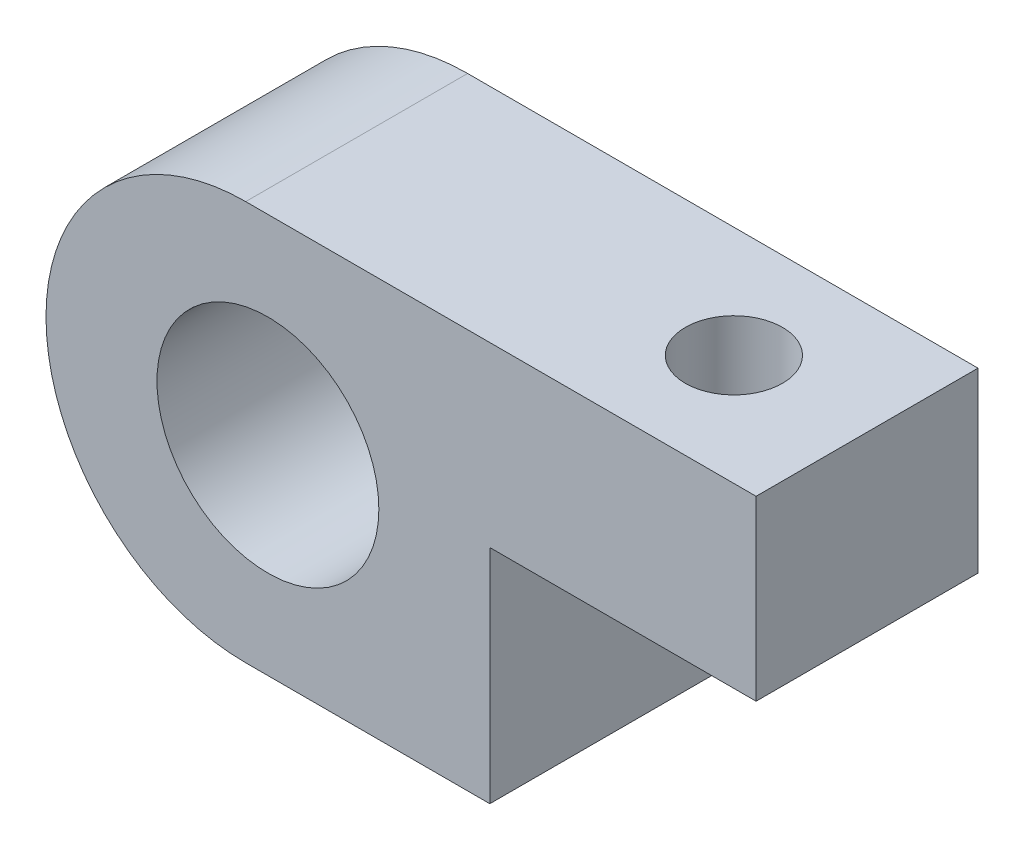
SolidWorks part; units mm, degrees
material "Magnesium Alloy"
ref_plane "Front Plane" through (0, 0, 0) normal (0, 0, 1) x (1, 0, 0)
ref_plane "Top Plane" through (0, 0, 0) normal (0, 1, 0) x (1, 0, 0)
ref_plane "Right Plane" through (0, 0, 0) normal (1, 0, 0) x (0, 0, -1)
sketch "Sketch2" plane through (0, 0, 0) normal (0, 0, 1) x (1, 0, 0)
  line L0 (0, 0) -> (40.64, 0)
  line L1 (40.64, 0) -> (40.64, -10.16)
  line L2 (40.64, -10.16) -> (25.4, -10.16)
  line L3 (25.4, -10.16) -> (25.4, -22.86)
  line L4 (25.4, -22.86) -> (0, -22.86)
  line L5 (0, -22.86) -> (0, 0)
  circle A0 centre (12.7, -11.43) radius 6.35
  dimension "D5" = 12.7
  dimension "D6" = 12.7
  dimension "D1" = 15.24
  dimension "D2" = 10.16
  dimension "D3" = 12.7
  dimension "D4" = 25.4
  dimension "D7" = 11.43
extrude "Boss-Extrude1" add sketch "Sketch2" along normal blind 12.7
fillet "Fillet3" radius 11.43 2 edges at (0, -22.86, 6.35) (0, 0, 6.35)
sketch "Sketch3" plane through (0, 0, 0) normal (0, 1, 0) x (1, 0, 0)
  line L0 (40.64, 0) -> (11.43, 0) construction
  line L1 (40.64, -12.7) -> (40.64, 0) construction
  circle A0 centre (33.02, -6.35) radius 2.54
  dimension "D1" = 6.35
  dimension "D2" = 7.62
hole_wizard "7/32 (0.21875) Diameter Hole1" positions "3DSketch1" profile "Sketch4" hole size "7/32" standard "ANSI Inch"
sketch3d "3DSketch1"
  point P0 (33.02, 0, 6.35)
  point P4 (33.02, 0, 6.35)
sketch "Sketch4" plane through (33.02, 0, 6.35) normal (1, 0, 0) x (0, 0, 1)
  line L0 (0, 0) -> (0, 38.1)
  line L1 (0, 38.1) -> (2.7781, 36.4307)
  line L2 (2.7781, 36.4307) -> (2.7781, 0)
  line L5 (2.7781, 0) -> (0, 0)
  line L10 (0, 38.1) -> (-2.7781, 36.4307) construction
  line L11 (0, -6.35) -> (0, 107.95) construction
  dimension "Hole Dia." = 5.5562
  dimension "Hole Depth" = 38.1
  dimension "Drill Angle" = 118
